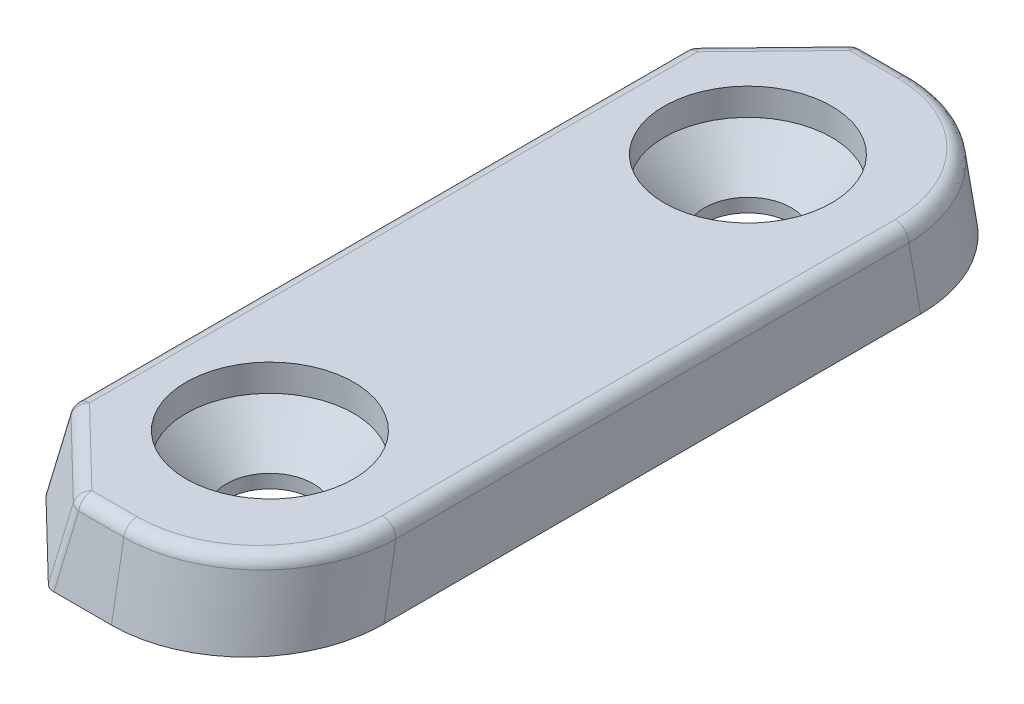
SolidWorks part; units mm, degrees
ref_plane "Спереди" through (0, 0, 0) normal (0, 0, 1) x (1, 0, 0)
ref_plane "Сверху" through (0, 0, 0) normal (0, 1, 0) x (1, 0, 0)
ref_plane "Справа" through (0, 0, 0) normal (1, 0, 0) x (0, 0, -1)
sketch "Эскиз1" plane through (0, 0, 0) normal (0, 1, 0) x (1, 0, 0)
  line L0 (0, 33.2845) -> (0, -21.3972) construction
  line L1 (0, 0) -> (27.1923, 0) construction
  line L3 (3.671, 15) -> (7.671, 15)
  line L4 (3.671, 15) -> (3.671, -15)
  line L5 (3.671, -15) -> (7.671, -15)
  line L6 (7.671, 15) -> (7.671, -15)
  line L7 (3.671, 15) -> (7.671, -15) construction
  line L8 (3.671, -15) -> (7.671, 15) construction
  point P4 (5.671, 0)
  dimension "D1" = 3.671
  dimension "D3" = 30
extrude "Бобышка-Вытянуть1" add sketch "Эскиз1" along normal blind 3 draft 10
sketch "Эскиз2" plane through (0, 0, 0) normal (0, 1, 0) x (1, 0, 0)
  line L3 (7.142, 14.471) -> (7.142, 15)
  line L4 (7.671, 15) -> (3.671, 15) construction
  line L5 (7.142, 15) -> (14.142, 15)
  line L6 (14.142, 15) -> (14.142, -15)
  line L7 (14.142, -15) -> (7.142, -15)
  line L8 (3.671, -15) -> (7.671, -15) construction
  line L9 (7.142, -15) -> (7.142, -14.471)
  line L10 (7.142, 14.471) -> (7.142, -14.471)
  dimension "D1" = 7
extrude "Бобышка-Вытянуть3" add sketch "Эскиз2" along normal up to surface (3 mm away) separate body up to face at (5.671, 3, 0)
sketch "Эскиз8" plane through (7.142, 0, 0) normal (-1, 0, 0) x (0, 0, 1)
  line L0 (-15, 3) -> (-15, 0)
  line L1 (-15, 0) -> (-14.471, 3)
  line L2 (-14.471, 3) -> (-15, 3)
  line L3 (14.471, 3) -> (15, 0)
  line L4 (15, 0) -> (15, 3)
  line L5 (15, 3) -> (14.471, 3)
extrude "Вырез-Вытянуть3" cut sketch "Эскиз8" against normal through all
combine bodies "Соединить1" operation type add bodies to combine 101 108
sketch "Эскиз6" plane through (0, 3, 0) normal (0, 1, 0) x (1, 0, 0)
  line L0 (0, 0) -> (8.8388, 8.8388) construction
  line L5 (0, 0) -> (0, 23.9923) construction
  circle A0 centre (8.8388, 8.8388) radius 1.6
  circle A2 centre (0, 0) radius 12.5 construction
  circle A3 centre (8.8388, -8.8388) radius 1.6
  circle A4 centre (-8.8388, -8.8388) radius 1.6 construction
  circle A5 centre (-8.8388, 8.8388) radius 1.6 construction
  point P0 (0, 0)
  dimension "D3" = 3.2
  dimension "D1" = 25
  dimension "D2" = 45
  dimension "D4" = 4
extrude "Вырез-Вытянуть2" cut sketch "Эскиз6" against normal through all
sketch "Эскиз9" plane through (0, 3, 0) normal (0, 1, 0) x (1, 0, 0)
  circle A0 centre (8.8388, 8.8388) radius 3.1
  circle A2 centre (8.8388, -8.8388) radius 3.1
  dimension "D1" = 6.2
  dimension "D2" = 6.2
extrude "Вырез-Вытянуть4" cut sketch "Эскиз9" against normal offset from surface (1 mm away) 2 up to face at (7.2388, 0, -8.8388)
chamfer "Фаска1" distance 1.5 angle 45 2 edges at (8.8388, 2, -7.2388) (8.8388, 2, 10.4388)
fillet "Скругление2" radius 5 2 edges at (14.142, 1.5, 14.7355) (14.142, 1.5, -14.7355)
chamfer "Фаска2" distance 3 angle 45 2 edges at (3.9355, 1.5, -14.7355) (3.9355, 1.5, 14.7355)
fillet "Скругление1" radius 0.5 12 edges at (8.1935, 3, -14.471) (14.142, 3, 0) (8.2415, 3, 14.471) (4.2, 3, 0.0481) (12.6776, 3, -12.984) (12.6776, 3, 12.984) (5.7705, 3, 12.9486) (7.0765, 1.5, 14.7355) (3.9355, 1.5, 11.6906) (6.9804, 1.5, -14.7355) (3.9355, 1.5, -11.5945) (5.7224, 3, -12.9005)
equation "\"motor_D\"= 49'Motor diameter"
equation "\"motor_H\"= 19'Motor heigh"
equation "\"motor_d1\"= 38.5'Seating diameter of screws on the fixed part of the motor"
equation "\"motor_s1\"= 2.5'Screws diameter on the fixed part of motor"
equation "\"motor_d2\"= 25'Seating diameter of screws on the moving part of the motor (if this parameter is not determine, write 0)"
equation "\"motor_a2\"= 0'Seating parameter in rectangle of screws on the moving part of the motor"
equation "\"motor_b2\"= 0'Seating parameter in rectangle of screws on the moving part of the motor"
equation "\"motor_s2\"= 3'Screws diameter on the moving part of motor"
equation "\"motor_cmd\"= 17'Central magnet mount diameter"
equation "\"motor_cmh\"= 1'Central magnet mount heigh (if not write 0)"
equation "\"motor_Dc\"= 5'Central hole diameter of motor"
equation "\"motor_whR\"= 17'Distance from center of motor to wires"
equation "\"bearing_d1\"= 8'Bearing inner diameter"
equation "\"bearing_d2\"= 16'Bearing external diameter"
equation "\"bearing h\"= 5'Bearing heigh"
equation "\"pin_d\"= 2'Pin diameter"
equation "\"pin_h\"= 13'Pin heigh"
equation "\"magnet_d1\"= 5'Magnet inner diameter"
equation "\"magnet_d2\"= 9.5'Magnet external diameter"
equation "\"magnet_h\"= 3'Magnet heigh"
equation "\"print_offset\"= 0.2'Offset for printing holes"
equation "\"ft_sensor_d1\"= 9.8"
equation "\"ft_sensor_d2\"= 24.9"
equation "\"ft_sensor_d3\"= 22.6'Inner diameter of "
equation "\"ft_sensor_h\"= 7.1"
equation "\"ft_sensor_whD\" = 5"
equation "\"D1@Эскиз1\"=(\"pin_d\"+6-(\"pin_d\"+1)*tan(10)*2)/2+0.2"
equation "\"D3@Эскиз1\"=30"
equation "\"D1@Бобышка-Вытянуть1\"=\"pin_d\"+1"
equation "\"D3@Эскиз6\"=\"motor_s2\"+\"print_offset\""
equation "\"D1@Эскиз6\"=\"motor_d2\""
equation "\"D1@Эскиз9\"=\"motor_s2\"+\"print_offset\"+3"
equation "\"D2@Эскиз9\"=\"D1@Эскиз9\""
